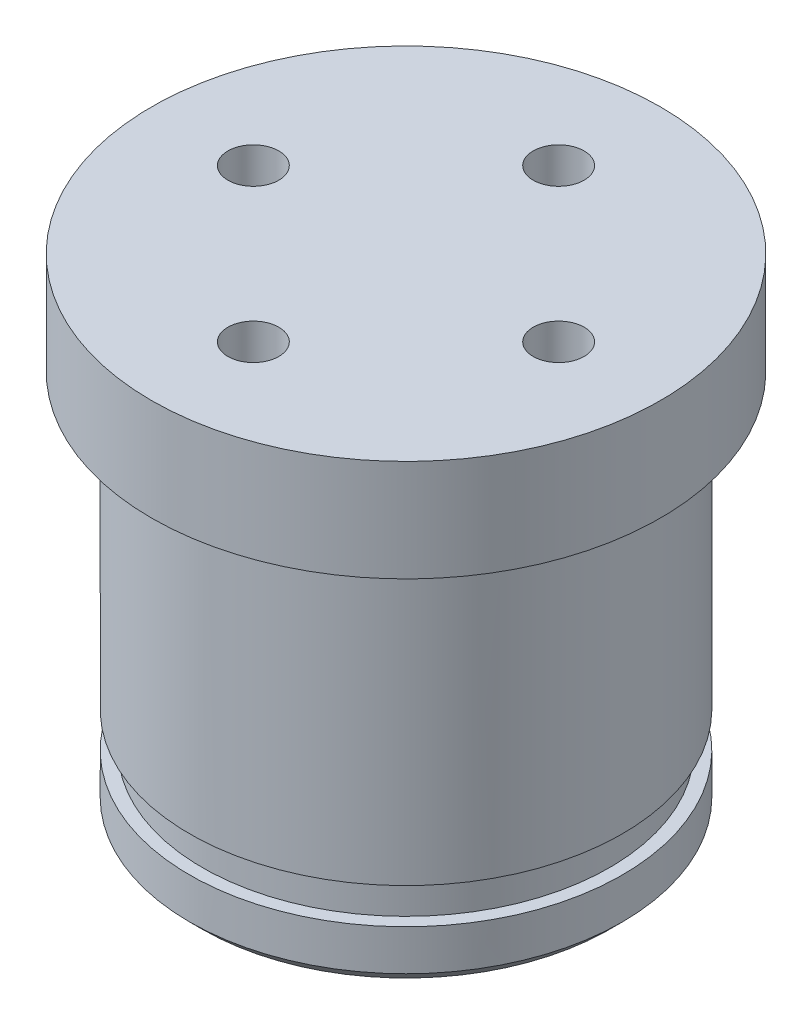
SolidWorks part; units mm, degrees
material "ABS"
ref_plane "Спереди" through (0, 0, 0) normal (0, 0, 1) x (1, 0, 0)
ref_plane "Сверху" through (0, 0, 0) normal (0, 1, 0) x (1, 0, 0)
ref_plane "Справа" through (0, 0, 0) normal (1, 0, 0) x (0, 0, -1)
sketch "Эскиз1" plane through (0, 0, 0) normal (0, 1, 0) x (1, 0, 0)
  circle A0 centre (0, 0) radius 8.5
  dimension "D1" = 17
extrude "Бобышка-Вытянуть1" add sketch "Эскиз1" along normal blind 15
sketch "Эскиз2" plane through (0, 15, 0) normal (0, 1, 0) x (1, 0, 0)
  circle A0 centre (0, 0) radius 10
  dimension "D1" = 20
extrude "Бобышка-Вытянуть2" add sketch "Эскиз2" along normal blind 4
sketch "Эскиз3" plane through (0, 0, 0) normal (0, -1, 0) x (1, 0, 0)
  circle A0 centre (0, 6) radius 1
  circle A1 centre (6, 0) radius 1
  circle A2 centre (0, -6) radius 1
  circle A3 centre (-6, 0) radius 1
  point P12 (0, 0)
  dimension "D1" = 2
  dimension "D2" = 6
  dimension "D3" = 4
extrude "Вырез-Вытянуть1" cut sketch "Эскиз3" against normal through all
sketch "Эскиз4" plane through (0, 0, 0) normal (0, -1, 0) x (1, 0, 0)
  circle A0 centre (0, 0) radius 8
  circle A1 centre (0, 0) radius 8.5
  dimension "D1" = 16
extrude "Вырез-Вытянуть2" cut sketch "Эскиз4" against normal blind 1.4 from offset 2.1 offset against normal yes
chamfer "Фаска1" distance 0.5 angle 45 1 edges at (0, 0, 8.5)
